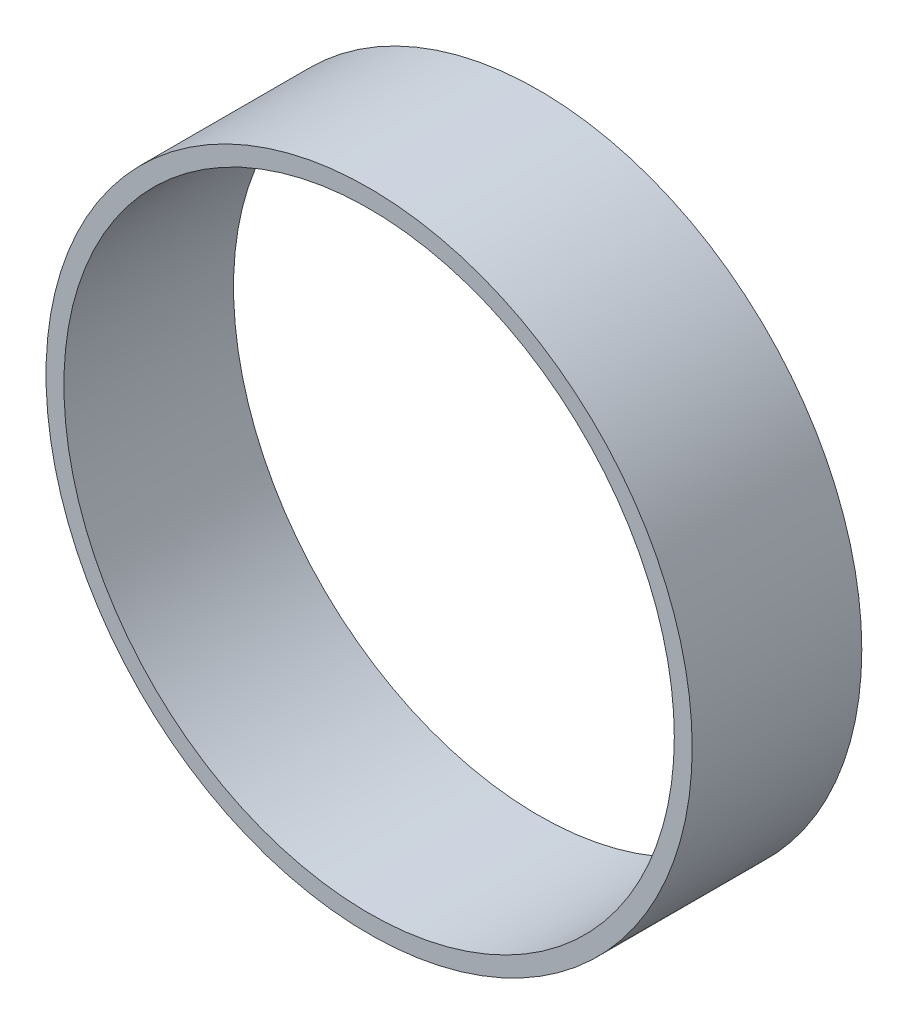
SolidWorks part; units mm, degrees
ref_plane "Front Plane" through (0, 0, 0) normal (0, 0, 1) x (1, 0, 0)
ref_plane "Top Plane" through (0, 0, 0) normal (0, 1, 0) x (1, 0, 0)
ref_plane "Right Plane" through (0, 0, 0) normal (1, 0, 0) x (0, 0, -1)
sketch "Sketch1" plane through (0, 0, 0) normal (0, 0, 1) x (1, 0, 0)
  circle A0 centre (0, 0) radius 38.1
  circle A1 centre (0, 0) radius 35.99
  dimension "D1" = 76.2
  dimension "D2" = 71.98
extrude "Boss-Extrude1" add sketch "Sketch1" along normal blind 20
